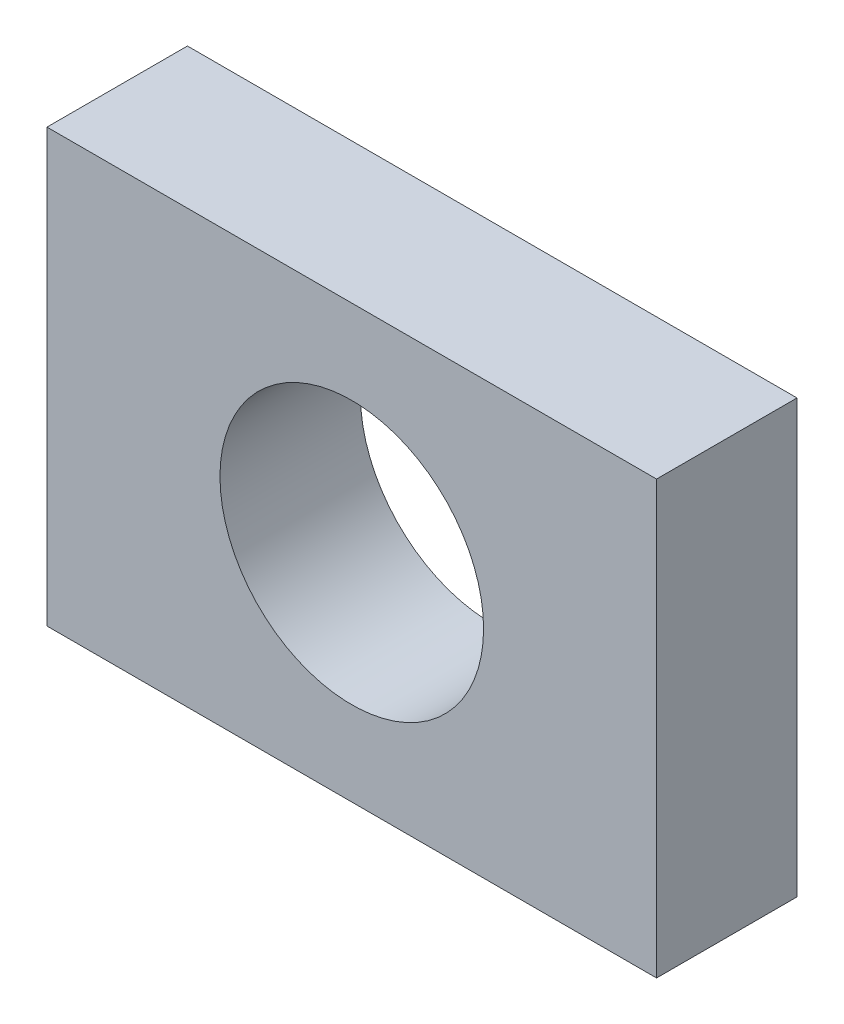
SolidWorks part; units mm, degrees
ref_plane "Front Plane" through (0, 0, 0) normal (0, 0, 1) x (1, 0, 0)
ref_plane "Top Plane" through (0, 0, 0) normal (0, 1, 0) x (1, 0, 0)
ref_plane "Right Plane" through (0, 0, 0) normal (1, 0, 0) x (0, 0, -1)
sketch "Sketch1" plane through (0, 0, 0) normal (0, 0, 1) x (1, 0, 0)
  line L1 (-55.1185, -39.0725) -> (55.1185, -39.0725)
  line L2 (-55.1185, -39.0725) -> (-55.1185, 39.0725)
  line L3 (-55.1185, 39.0725) -> (55.1185, 39.0725)
  line L4 (55.1185, -39.0725) -> (55.1185, 39.0725)
  line L5 (-55.1185, -39.0725) -> (55.1185, 39.0725) construction
  line L6 (-55.1185, 39.0725) -> (55.1185, -39.0725) construction
  point P0 (0, 0)
extrude "Boss-Extrude1" add sketch "Sketch1" against normal blind 25.4
sketch "Sketch2" plane through (0, 0, 0) normal (0, 0, 1) x (1, 0, 0)
  circle A0 centre (0, 0) radius 23.8373
extrude "Cut-Extrude1" cut sketch "Sketch2" against normal through all
